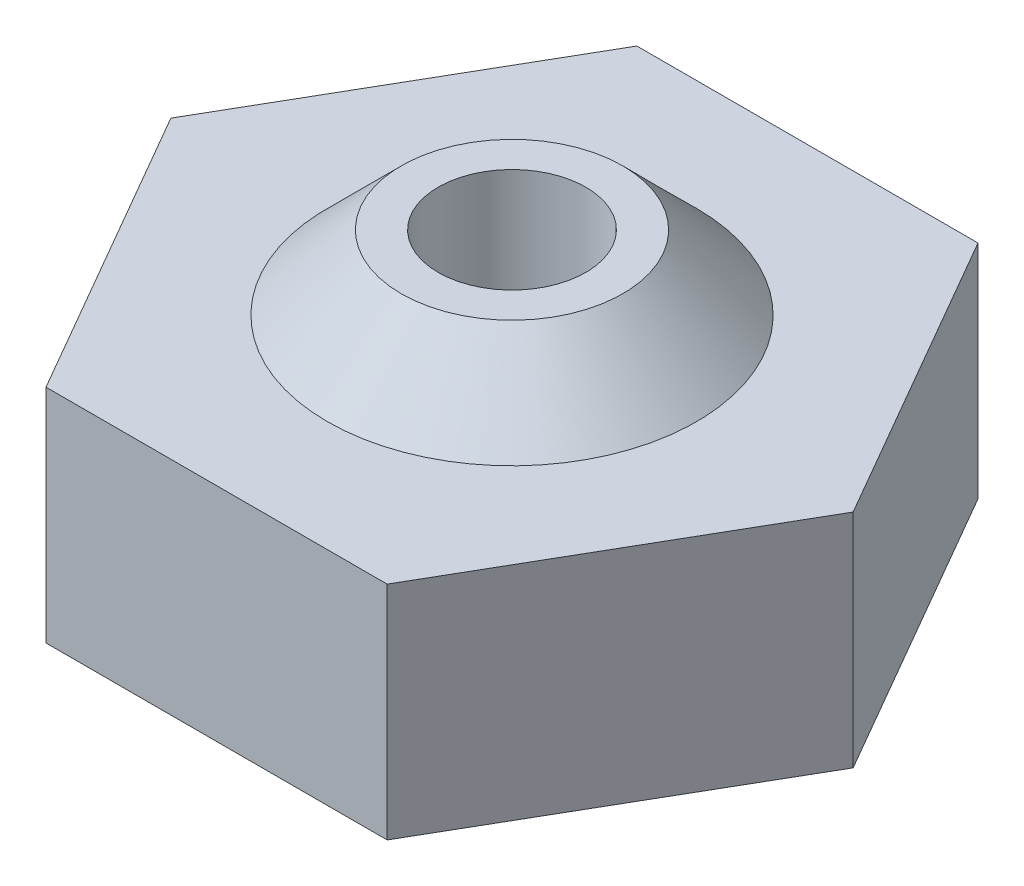
SolidWorks part; units mm, degrees
material "Plain Carbon Steel"
ref_plane "Front" through (0, 0, 0) normal (0, 0, 1) x (1, 0, 0)
ref_plane "Top" through (0, 0, 0) normal (0, 1, 0) x (1, 0, 0)
ref_plane "Right" through (0, 0, 0) normal (1, 0, 0) x (0, 0, -1)
sketch "Sketch1" plane through (0, 0, 0) normal (0, 1, 0) x (1, 0, 0)
  line L1 (11.547, 20) -> (-11.547, 20)
  line L2 (-11.547, 20) -> (-23.094, 0)
  line L3 (-23.094, 0) -> (-11.547, -20)
  line L4 (-11.547, -20) -> (11.547, -20)
  line L5 (11.547, -20) -> (23.094, 0)
  line L6 (23.094, 0) -> (11.547, 20)
  circle A0 centre (0, 0) radius 20 construction
  circle A1 centre (0, 0) radius 10 construction
  dimension "D2" = 20
  dimension "D1" = 40
extrude "Boss-Extrude1" add sketch "Sketch1" along normal blind 15
sketch "Sketch2" plane through (0, 15, 0) normal (0, 1, 0) x (1, 0, 0)
  circle A0 centre (0, 0) radius 12.5
  dimension "D1" = 25
extrude "Boss-Extrude2" add sketch "Sketch2" along normal blind 5
sketch "Sketch3" plane through (0, 20, 0) normal (0, 1, 0) x (1, 0, 0)
  circle A0 centre (0, 0) radius 5
  dimension "D1" = 10
extrude "Cut-Extrude1" cut sketch "Sketch3" against normal through all
chamfer "Chamfer1" distance 5 angle 45 1 edges at (0, 20, 12.5)
sketch "Sketch4" plane through (0, 0, 0) normal (0, -1, 0) x (1, 0, 0)
  circle A0 centre (0, 0) radius 12.5
  dimension "D1" = 25
extrude "Cut-Extrude2" cut sketch "Sketch4" against normal blind 5
